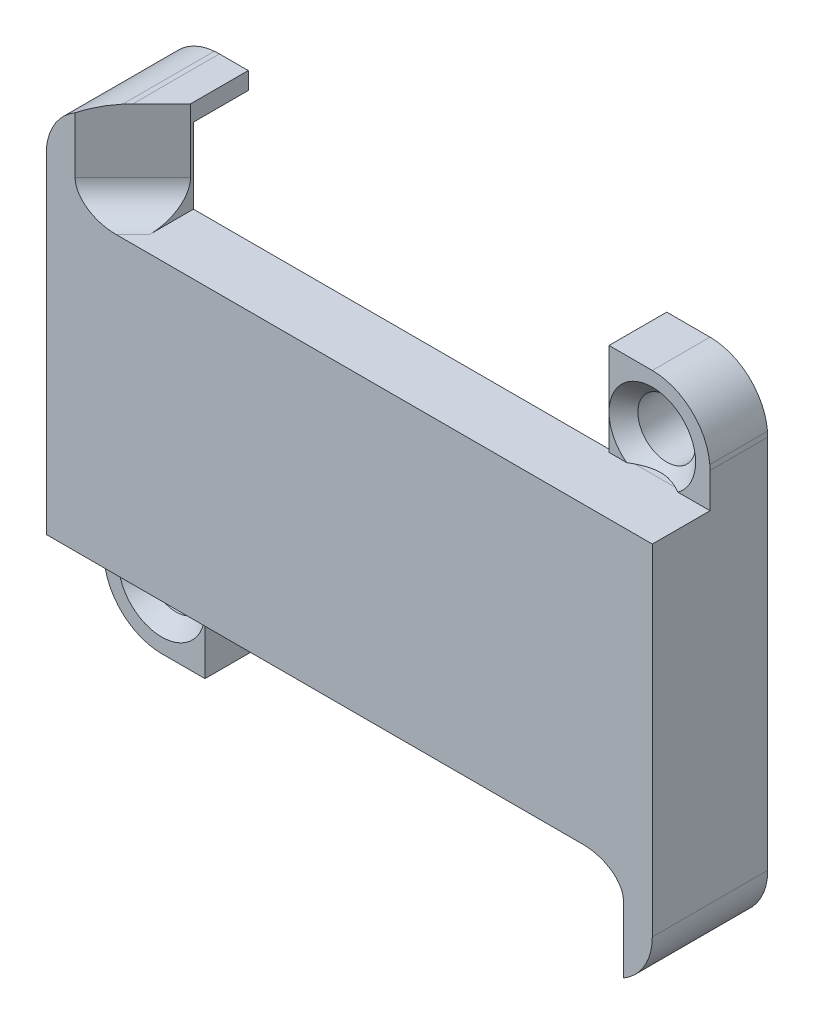
SolidWorks part; units mm, degrees
ref_plane "Top Plane" through (0, 0, 0) normal (0, 0, 1) x (1, 0, 0)
ref_plane "Right Plane" through (0, 0, 0) normal (0, 1, 0) x (1, 0, 0)
ref_plane "Front Plane" through (0, 0, 0) normal (1, 0, 0) x (0, 0, -1)
sketch "Sketch1" plane through (0, 0, 0) normal (0, 0, 1) x (1, 0, 0)
  line L0 (0.6, 14) -> (0.6, 3.577)
  line L3 (20.4, 3) -> (20.4, 13.79)
  line L7 (0, 15) -> (0, 2)
  line L8 (2, 0) -> (19, 0)
  line L9 (19, 0) -> (19.1743, 0.0076)
  line L10 (21, 2) -> (21, 15)
  line L11 (21, 15) -> (20.9924, 15.1743)
  line L12 (19, 17) -> (2, 17)
  line L13 (2, 17) -> (1.8257, 16.9924)
  line L14 (0, 15) -> (0, 2)
  line L15 (2, 0) -> (3.5, 0)
  line L16 (19, 0) -> (19.1743, 0.0076)
  line L17 (21, 2) -> (21, 15)
  line L18 (21, 15) -> (20.9924, 15.1743)
  line L19 (19, 17) -> (17.5, 17)
  line L20 (2, 17) -> (1.8257, 16.9924)
  line L21 (3.5, 0) -> (3.5, 3.577)
  line L22 (3.5, 3.577) -> (0.6, 3.577)
  line L23 (18, 0.6) -> (18, 0)
  line L24 (5.623, 4.077) -> (1.975, 4.077) construction
  line L25 (17.5, 17) -> (17.5, 13.79)
  line L26 (0.6, 15) -> (0.6, 2) construction
  line L27 (2, 0.6) -> (18.9869, 0.6) construction
  line L28 (17.5, 13.79) -> (20.4, 13.79)
  line L29 (19.45, 13.59) -> (19.15, 13.59) construction
  line L30 (20.4, 3) -> (18, 0.6)
  line L31 (20.4, 2) -> (20.4, 14.9869) construction
  line L32 (20.4, 14.9869) -> (20.3936, 15.1339) construction
  line L33 (19, 16.4) -> (2.0131, 16.4) construction
  line L34 (18.9869, 0.6) -> (19.1339, 0.6064) construction
  line L35 (20.4, 3) -> (20.4, 0.6) construction
  line L36 (20.4, 0.6) -> (18, 0.6) construction
  line L37 (2, 0) -> (19, 0) construction
  line L38 (18, 0) -> (19, 0)
  line L39 (20.4, 3) -> (21, 3) construction
  line L40 (2, 0) -> (19, 0) construction
  line L41 (3, 16.4) -> (0.6, 14)
  line L42 (0.6, 14) -> (0.6, 16.4) construction
  line L43 (0.6, 16.4) -> (3, 16.4) construction
  line L44 (3, 16.4) -> (3, 17)
  line L45 (2.0131, 16.4) -> (1.8661, 16.3936) construction
  line L46 (19, 17) -> (2, 17) construction
  line L47 (3, 17) -> (2, 17)
  line L48 (0.6, 14) -> (0, 14) construction
  line L49 (19, 17) -> (2, 17) construction
  arc A4 (0, 2) -> (2, 0) centre (2, 2) ccw
  arc A5 (19.1743, 0.0076) -> (21, 2) centre (19, 2) ccw
  arc A6 (20.9924, 15.1743) -> (19, 17) centre (19, 15) ccw
  arc A7 (1.8257, 16.9924) -> (0, 15) centre (2, 15) ccw
  arc A8 (0, 2) -> (2, 0) centre (2, 2) ccw
  arc A9 (19.1743, 0.0076) -> (21, 2) centre (19, 2) ccw
  arc A10 (20.9924, 15.1743) -> (19, 17) centre (19, 15) ccw
  arc A11 (1.8257, 16.9924) -> (0, 15) centre (2, 15) ccw
  circle A12 centre (2, 2) radius 1 construction
  arc A13 (0.6, 2) -> (2, 0.6) centre (2, 2) ccw construction
  circle A14 centre (19, 15) radius 1 construction
  arc A15 (20.3936, 15.1339) -> (19, 16.4) centre (19, 15) ccw construction
  circle A16 centre (19, 15) radius 1
  circle A17 centre (2, 2) radius 1
  arc A22 (19.1339, 0.6064) -> (20.4, 2) centre (19, 2) ccw construction
  arc A23 (1.8661, 16.3936) -> (0.6, 15) centre (2, 15) ccw construction
  point P42 (19.3, 13.59)
  dimension "D3" = 0.5
  dimension "D4" = 0.5
  dimension "D5" = 0.2
  dimension "D6" = 0.5
  dimension "D7" = 2.4
  dimension "D1" = 0
  dimension "D2" = 0.6
extrude "Boss-Extrude2" add sketch "Sketch1" along normal blind 2 contours L16 A9 L17 L18 A10 L19 L25 L28 L3 L30 L23 L38 | L14 A8 L15 L21 L22 L0 L41 L44 L47 L20 A11 | A17 | A16
sketch "Sketch2" plane through (0, 0, 2) normal (0, 0, 1) x (1, 0, 0)
  line L0 (3, 13.79) -> (21, 13.79)
  line L1 (18, 0) -> (18, 3.577)
  line L2 (3, 13.79) -> (3, 16.4)
  line L3 (3, 16.4) -> (0.6, 14) construction
  line L4 (3, 16.4) -> (3, 17)
  line L6 (18, 3.577) -> (0, 3.577)
  line L7 (0, 15) -> (0, 2)
  line L8 (2, 0) -> (19, 0)
  line L9 (19, 0) -> (19.1743, 0.0076)
  line L10 (21, 2) -> (21, 15)
  line L11 (21, 15) -> (20.9924, 15.1743)
  line L12 (19, 17) -> (2, 17)
  line L13 (2, 17) -> (1.8257, 16.9924)
  line L14 (0, 15) -> (0, 3.577)
  line L15 (18, 0) -> (19, 0)
  line L16 (19, 0) -> (19.1743, 0.0076)
  line L17 (21, 2) -> (21, 13.79)
  line L19 (3, 17) -> (2, 17)
  line L20 (2, 17) -> (1.8257, 16.9924)
  line L21 (3.5, 3.577) -> (0.6, 3.577) construction
  line L22 (17.5, 13.79) -> (20.4, 13.79) construction
  arc A4 (0, 2) -> (2, 0) centre (2, 2) ccw
  arc A5 (19.1743, 0.0076) -> (21, 2) centre (19, 2) ccw
  arc A6 (20.9924, 15.1743) -> (19, 17) centre (19, 15) ccw
  arc A7 (1.8257, 16.9924) -> (0, 15) centre (2, 15) ccw
  arc A9 (19.1743, 0.0076) -> (21, 2) centre (19, 2) ccw
  arc A11 (1.8257, 16.9924) -> (0, 15) centre (2, 15) ccw
  dimension "D1" = 0
extrude "Boss-Extrude5" add sketch "Sketch2" against normal blind 0.1 and the other way blind 2
chamfer "Chamfer1" distance 2 angle 45 2 edges at (18, 1.7885, 4) (3, 15.395, 4)
fillet "Fillet1" radius 1 2 edges at (19, 3.577, 3) (2, 13.79, 3)
chamfer "Chamfer2" distance 0.5 angle 45 2 edges at (20, 15, 2) (3, 2, 2)
